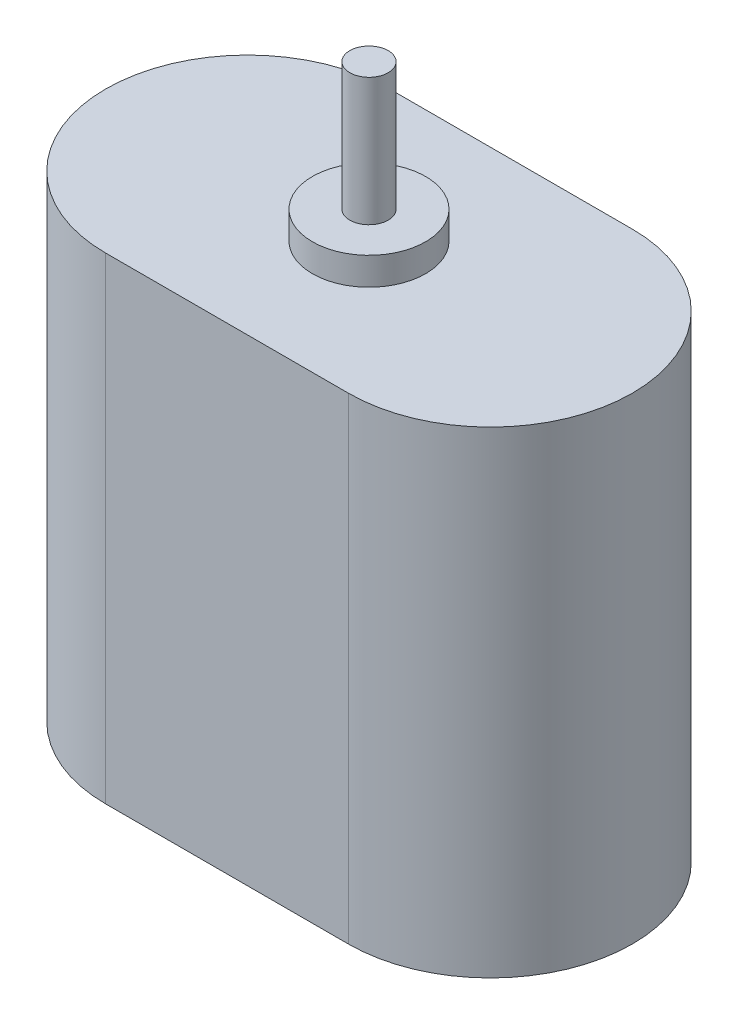
SolidWorks part; units mm, degrees
material "Cast Alloy Steel"
ref_plane "Front Plane" through (0, 0, 0) normal (0, 0, 1) x (1, 0, 0)
ref_plane "Top Plane" through (0, 0, 0) normal (0, 1, 0) x (1, 0, 0)
ref_plane "Right Plane" through (0, 0, 0) normal (1, 0, 0) x (0, 0, -1)
sketch "Sketch1" plane through (0, 0, 0) normal (0, 1, 0) x (1, 0, 0)
  line L0 (-1270.7662, 0) -> (1270.7662, 0) construction
  line L1 (-6.35, -7.4295) -> (6.35, -7.4295)
  line L2 (-6.35, -7.4295) -> (-6.35, 7.4295)
  line L3 (-6.35, 7.4295) -> (6.35, 7.4295)
  line L4 (6.35, -7.4295) -> (6.35, 7.4295)
  line L5 (0, -1132.7247) -> (0, 1132.7247) construction
  arc A1 (-6.35, 7.4295) -> (-6.35, -7.4295) centre (-6.35, 0) ccw
  arc A3 (6.35, -7.4295) -> (6.35, 7.4295) centre (6.35, 0) ccw
  point P0 (0, 0)
  point P6 (0, 7.4295)
  point P10 (-6.35, 7.4295)
  point P13 (6.35, 7.4295)
  dimension "D1" = 12.7
  dimension "D3" = 14.859
extrude "Boss-Extrude1" add sketch "Sketch1" along normal blind 24.9555 contours L2 A1 | L1 L4 L3 L2 | L4 A3 region at (0, 0, 0) region at (-9.5032, 0, 0) region at (9.5032, 0, 0)
sketch "Sketch2" plane through (0, 24.9555, 0) normal (0, 1, 0) x (1, 0, 0)
  circle A0 centre (0, 0) radius 2.9604
  circle A1 centre (0, 0) radius 1.0033
  dimension "D1" = 5.9207
  dimension "D2" = 2.0066
extrude "Boss-Extrude2" add sketch "Sketch2" along normal blind 1.4478
extrude "Boss-Extrude3" add sketch "Sketch2<3>" along normal blind 8.128 contours A1 region at (0, 24.9555, 0)
sketch "Sketch2<3>" plane through (0, 24.9555, 0) normal (0, 1, 0) x (1, 0, 0) same geometry as "Sketch2"
sketch "Sketch3" plane through (0, 0, 0) normal (0, -1, 0) x (1, 0, 0)
  line L0 (-2.8153, -4.0132) -> (2.8153, -4.0132)
  arc A0 (2.8153, -4.0132) -> (-2.8153, -4.0132) centre (0, 0) ccw
  point P3 (0, 4.9022)
  dimension "D1" = 8.9154
  dimension "D2" = 9.8044
extrude "Boss-Extrude4" add sketch "Sketch3" along normal blind 1.905
